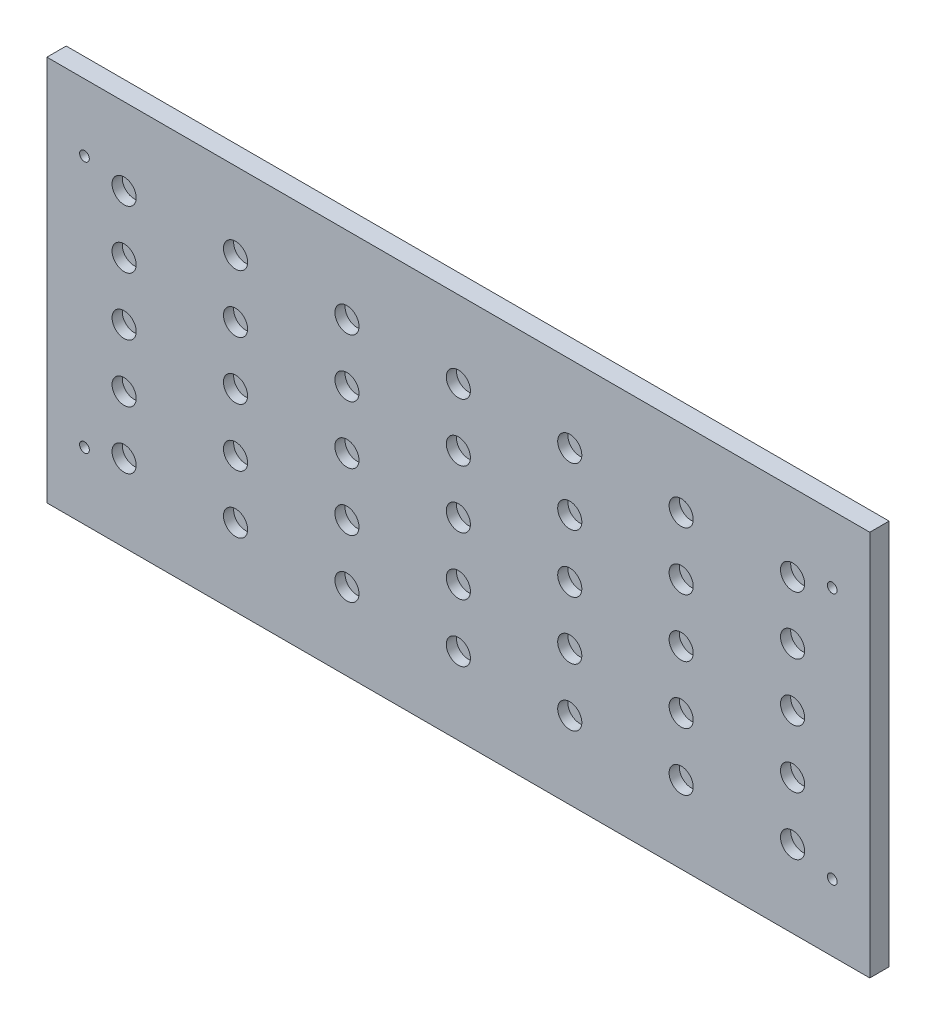
SolidWorks part; units mm, degrees
ref_plane "Front Plane" through (0, 0, 0) normal (0, 0, 1) x (1, 0, 0)
ref_plane "Top Plane" through (0, 0, 0) normal (0, 1, 0) x (1, 0, 0)
ref_plane "Right Plane" through (0, 0, 0) normal (1, 0, 0) x (0, 0, -1)
sketch "Sketch1" plane through (0, 0, 0) normal (0, 0, 1) x (1, 0, 0)
  line L0 (135.35, 127) -> (135.35, 0) construction
  line L1 (0, 0) -> (270.7, 0)
  line L2 (0, 0) -> (0, 127)
  line L3 (0, 127) -> (270.7, 127)
  line L4 (270.7, 0) -> (270.7, 127)
  line L5 (0, 63.5) -> (270.7, 63.5) construction
  circle A3 centre (12.35, 105) radius 1.6
  circle A7 centre (258.35, 105) radius 1.6
  circle A8 centre (258.35, 22) radius 1.6
  circle A9 centre (12.35, 22) radius 1.6
  dimension "D11" = 3.2
  dimension "D1" = 127
  dimension "D2" = 270.7
  dimension "D12" = 12.35
  dimension "D13" = 22
extrude "Wall" add sketch "Sketch1" along normal blind 6.35
sketch "Sketch2" plane through (0, 0, 6.35) normal (0, 0, 1) x (1, 0, 0)
  line L0 (135.35, 127) -> (135.35, 98.425) construction
  line L1 (270.7, 127) -> (0, 127) construction
  line L2 (135.35, 98.425) -> (66.6667, 98.425) construction
  line L3 (135.35, 98.425) -> (204.0333, 98.425) construction
  line L4 (0, 127) -> (0, 0) construction
  circle A0 centre (135.35, 98.425) radius 3.9687
  circle A1 centre (66.6667, 98.425) radius 3.9688
  circle A2 centre (204.0333, 98.425) radius 3.9687
  dimension "D2" = 7.9375
  dimension "D1" = 28.575
  dimension "D3" = 66.6667
extrude "RodSupportCutouts" [suppressed] cut sketch "Sketch2" against normal up to next
sketch "Sketch3" plane through (0, 0, 6.35) normal (0, 0, 1) x (1, 0, 0)
  line L1 (25.4, 88.9) -> (245.3, 88.9)
  line L2 (25.4, 88.9) -> (25.4, 114.3)
  line L3 (25.4, 114.3) -> (245.3, 114.3)
  line L4 (245.3, 88.9) -> (245.3, 114.3)
  line L5 (25.4, 88.9) -> (245.3, 114.3) construction
  line L6 (25.4, 114.3) -> (245.3, 88.9) construction
  line L7 (270.7, 127) -> (0, 127) construction
  line L8 (0, 127) -> (0, 0) construction
  point P0 (135.35, 101.6)
  point P9 (135.35, 127)
  dimension "D1" = 25.4
  dimension "D2" = 25.4
  dimension "D3" = 25.4
extrude "CannulaLargeCutout" [suppressed] cut sketch "Sketch3" against normal up to next
sketch "Sketch4" [suppressed] plane through (0, 0, 9.525) normal (0, 0, 1) x (1, 0, 0)
  line L0 (6, 103.5) -> (194, 103.5) construction
  line L1 (6, 105) -> (6, 22) construction
  line L2 (194, 105) -> (194, 22) construction
  line L3 (200, 127) -> (0, 127) construction
  line L4 (0, 127) -> (0, 0) construction
  circle A0 centre (60, 103.5) radius 6.35
  circle A1 centre (20, 103.5) radius 6.35
  circle A2 centre (100, 103.5) radius 6.35
  circle A3 centre (140, 103.5) radius 6.35
  circle A4 centre (60, 63.5) radius 6.35
  circle A5 centre (100, 63.5) radius 6.35
  circle A6 centre (140, 63.5) radius 6.35
  circle A7 centre (60, 23.5) radius 6.35
  circle A8 centre (100, 23.5) radius 6.35
  circle A9 centre (140, 23.5) radius 6.35
  circle A10 centre (20, 63.5) radius 6.35
  circle A11 centre (20, 23.5) radius 6.35
  circle A12 centre (180, 103.5) radius 6.35
  circle A13 centre (180, 63.5) radius 6.35
  circle A14 centre (180, 23.5) radius 6.35
  point P42 (100, 127)
  point P45 (0, 63.5)
  dimension "D3" = 12.7
  dimension "D1" = 5
  dimension "D2" = 3
extrude "CannulaHoles" [suppressed] cut sketch "Sketch4" against normal up to next
ref_plane "LeftBoundary" through (25.4, 0, 0) normal (-1, 0, 0) x (0, 0, 1)
ref_plane "RightBoundary" through (245.3, 0, 0) normal (1, 0, 0) x (0, 0, -1)
ref_plane "TopBoundary" through (0, 101.6, 0) normal (0, 1, 0) x (1, 0, 0)
ref_plane "BottomBoundary" through (0, 25.4, 0) normal (0, -1, 0) x (-1, 0, 0)
sketch "Sketch5" plane through (0, 0, 6.35) normal (0, 0, 1) x (1, 0, 0)
  line L4 (25.4, 3.4925) -> (25.4, -3.4925) construction
  line L5 (3.4925, 101.6) -> (-3.4925, 101.6) construction
  circle A0 centre (25.4, 101.6) radius 3.9687
  dimension "D1" = 7.9375
extrude "RodSupportCutout" cut sketch "Sketch5" against normal blind 3.35
pattern_linear "SupportPattern" count 7 spacing 36.65 along (1, 0, 0) count 5 spacing 19.05 along (0, -1, 0) of "RodSupportCutout"
equation "\"Length\"= 283mm"
equation "\"Width\"= 225mm"
equation "\"WallThickness\"= 0.25in"
equation "\"UpperWaterJacketThickness\"= 28mm"
equation "\"SpacerHeight\"= 80.2mm"
equation "\"SpacerCornerWidth\"= 10mm"
equation "\"SpacerCornerHeight\"= 60.16mm"
equation "\"SpacerPegDiameter\"= 10mm"
equation "\"SpacerPegHeight\"= 10mm"
equation "\"TubingShort\"= 110mm"
equation "\"TubingLong\"= 175mm"
equation "\"PlateLength\"= 252mm"
equation "\"PlateWidth\"= 190mm"
equation "\"PlateHoleDiameter\"= 5.9mm"
equation "\"PlateHoleBottom\"= 2mm"
equation "\"PlateHoleSide\"= 1.55mm"
equation "\"PlateHoleSpacing\"= 3.1mm"
equation "\"PlateThickness\"= 1.55mm"
equation "\"ReservoirBottom\"= 12.5mm"
equation "\"ReservoirSupportWidth\"= 12mm"
equation "\"ReservoirSupportHeight\"= 15.1mm"
equation "\"ReservoirSupportPlacementHeight\"= 50mm"
equation "\"ReservoirHoleDiameter\"= 12.7mm"
equation "\"ReservoirHoleRight\"= 25mm"
equation "\"ReservoirHoleTop\"= \"ReservoirSupportPlacementHeight\""
equation "\"ReservoirHeight\"= 90mm"
equation "\"ReservoirPortBottom\"= 4mm"
equation "\"ReservoirPortTop\"= 10mm"
equation "\"ReservoirPortWidth\"= 101mm"
equation "\"CustomSpacerHeight\"= 5in"
equation "\"CustomSpacerRodHoleHeight\"= .75in"
equation "\"CustomSpacerRodHoleDiameter\"= .3125in"
equation "\"ScrewBlockSide\"= 12mm"
equation "\"ScrewBlockUpperHeight\"= 16mm"
equation "\"ScrewBlockLowerHeight\"= 16mm"
equation "\"InternalLength\"= 258mm"
equation "\"InternalWidth\"= 200mm"
equation "\"CustomSpacerPegHeight\"= 1in"
equation "\"CustomSpacerScrewBore\"=3.2mm"
equation "\"CustomSpacerScrewDepth\"=10mm"
equation "\"D1@Sketch1\"=\"CustomSpacerHeight\""
equation "\"D2@Sketch1\"=\"WallLength\""
equation "\"D11@Sketch1\"=\"CustomSpacerScrewBore\""
equation "\"D12@Sketch1\"  = \"ScrewBlockSide\"/2 + \"WallThickness\""
equation "\"D13@Sketch1\"=\"ScrewBlockUpperHeight\"+\"ScrewBlockSide\"/2"
equation "\"D1@Wall\" = \"WallThickness\""
equation "\"D1@Sketch2\"=\"CustomSpacerRodHoleHeight\" + \"CustomSpacerRodHoleDiameter\" +0.0625in"
equation "\"D2@Sketch2\"=\"CustomSpacerRodHoleDiameter\""
equation "\"D3@Sketch2\"=\"InternalWidth\" / 3"
equation "\"D1@Sketch3\"=1in"
equation "\"WallLength\"= \"InternalLength\" + ( 2 * \"WallThickness\" )"
equation "\"D1@Sketch5\"=\"CustomSpacerRodHoleDiameter\""
equation "\"D1@RodSupportCutout\"=\"WallThickness\" - 3"
